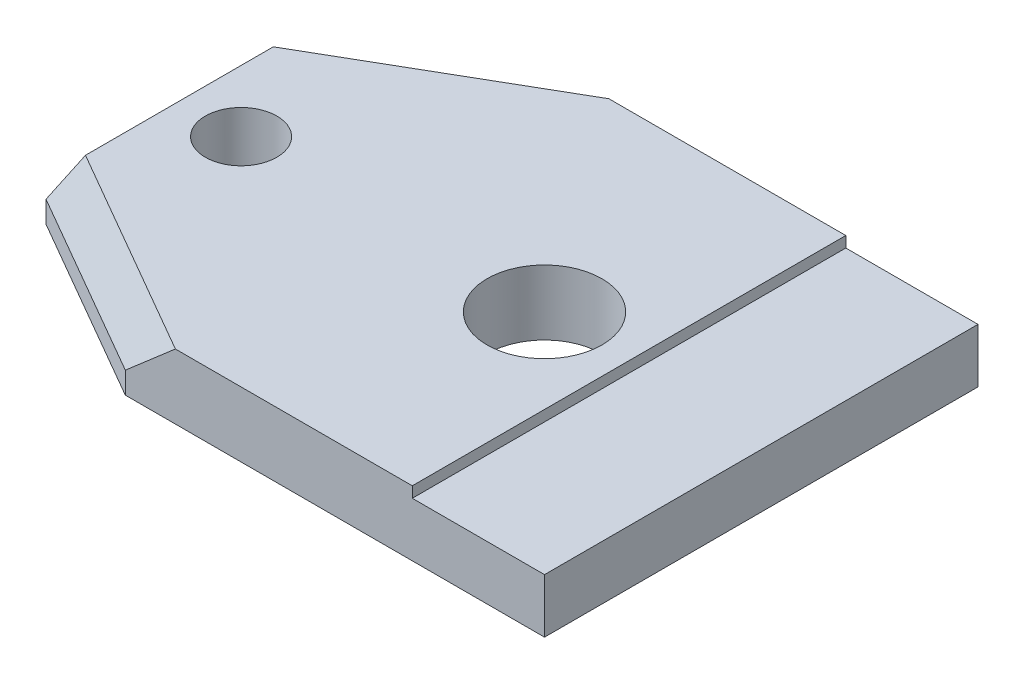
SolidWorks part; units mm, degrees
material "ABS"
ref_plane "Ebene vorne" through (0, 0, 0) normal (0, 0, 1) x (1, 0, 0)
ref_plane "Ebene oben" through (0, 0, 0) normal (0, 1, 0) x (1, 0, 0)
ref_plane "Ebene rechts" through (0, 0, 0) normal (1, 0, 0) x (0, 0, -1)
sketch "Skizze1" plane through (0, 0, 0) normal (0, 0, 1) x (1, 0, 0)
  line L0 (0, 0) -> (28, 0)
  line L1 (28, 0) -> (28, 2.5)
  line L2 (28, 2.5) -> (21.9, 2.5)
  line L3 (21.9, 2.5) -> (21.9, 3)
  line L4 (21.9, 3) -> (0, 3)
  line L5 (0, 3) -> (0, 0)
  line L6 (18, 3) -> (18, 0) construction
  line L7 (4, 3) -> (4, 0) construction
  line L8 (14, 3) -> (14, 0) construction
  line L9 (14, 0) -> (14, -6.2) construction
  line L10 (14, -6.2) -> (28, -6.2) construction
  line L11 (28, -6.2) -> (28, 0) construction
  line L12 (14, -6.2) -> (0, -6.2) construction
  line L13 (0, -6.2) -> (0, 0) construction
  line L14 (4, 0) -> (4, -6.2) construction
  circle A0 centre (4, 3) radius 1.65 construction
  circle A1 centre (18, 3) radius 2.65 construction
  dimension "D11" = 3.3
  dimension "D12" = 5.3
  dimension "D1" = 6.1
  dimension "D2" = 3
  dimension "D3" = 2.5
  dimension "D4" = 4
  dimension "D5" = 10
  dimension "D6" = 4
  dimension "D7" = 10
  dimension "D8" = 28
  dimension "D9" = 6.2
  dimension "D10" = 14
extrude "Aufsatz-Linear austragen1" add sketch "Skizze1" along normal blind 20
sketch "Skizze2" plane through (0, 0, 0) normal (0, -1, 0) x (1, 0, 0)
  line L0 (0, 10) -> (28, 10) construction
  line L1 (0, 20) -> (0, 0) construction
  line L2 (28, 20) -> (28, 0) construction
  circle A0 centre (4, 10) radius 1.65
  circle A1 centre (18, 10) radius 2.65
  dimension "D3" = 3.3
  dimension "D4" = 5.3
  dimension "D1" = 4
  dimension "D2" = 10
extrude "Schnitt-Linear austragen1" cut sketch "Skizze2" against normal up to surface (3 mm away) up to face at (10.95, 3, 10)
chamfer "Fase1" distance 5 angle 60 2 edges at (0, 1.5, 0) (0, 1.5, 20) first distance on face at (0, 1.5, 10)
chamfer "Fase2" distance 2 angle 30 3 edges at (4.3301, 3, 17.5) (4.3301, 3, 2.5) (0, 3, 10) first distance on face at (4.3301, 1.5, 17.5) first distance on face at (4.3301, 1.5, 2.5) first distance on face at (0, 1.5, 10)
